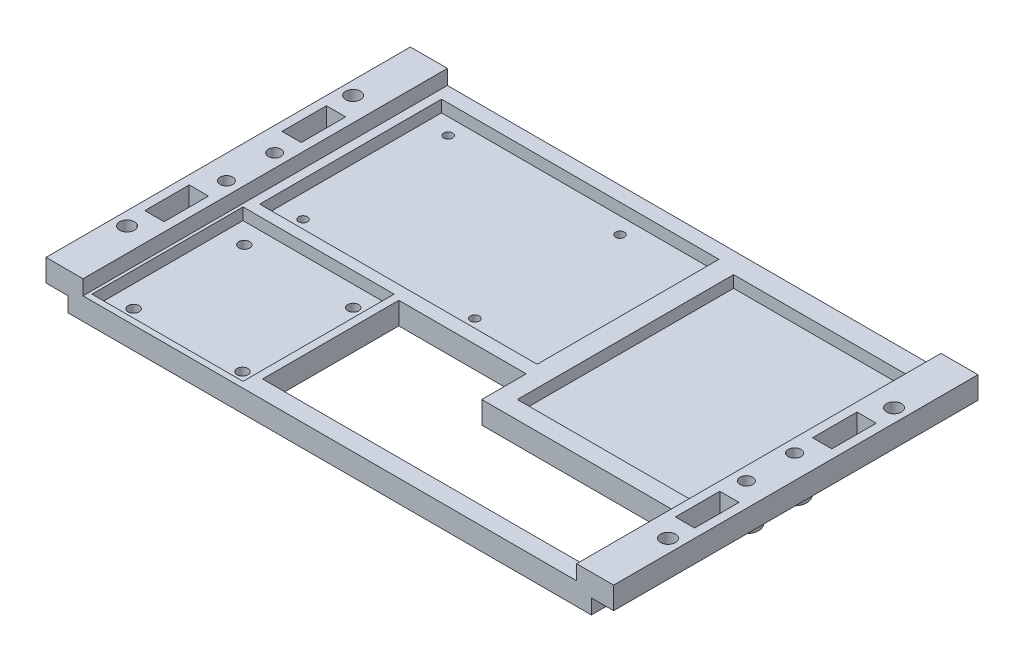
SolidWorks part; units mm, degrees
ref_plane "Front Plane" through (0, 0, 0) normal (0, 0, 1) x (1, 0, 0)
ref_plane "Top Plane" through (0, 0, 0) normal (0, 1, 0) x (1, 0, 0)
ref_plane "Right Plane" through (0, 0, 0) normal (1, 0, 0) x (0, 0, -1)
sketch "Sketch2" plane through (0, 0, 0) normal (0, 0, 1) x (1, 0, 0)
  line L0 (179.1, 12.5) -> (191.6, 12.5)
  line L1 (7.5, 0) -> (184.1, 0)
  line L2 (0, 5) -> (0, 12.5)
  line L3 (0, 12.5) -> (12.5, 12.5)
  line L4 (191.6, 5) -> (191.6, 12.5)
  line L7 (0, 5) -> (7.5, 5)
  line L8 (7.5, 0) -> (7.5, 5)
  line L11 (191.6, 5) -> (184.1, 5)
  line L12 (184.1, 0) -> (184.1, 5)
  line L14 (12.5, 12.5) -> (12.5, 7.5)
  line L15 (12.5, 7.5) -> (179.1, 7.5)
  line L16 (179.1, 12.5) -> (179.1, 7.5)
  dimension "D1" = 191.6
  dimension "D2" = 5
  dimension "D3" = 5
  dimension "D4" = 5
  dimension "D5" = 12.5
  dimension "D6" = 7.5
  dimension "D7" = 7.5
  dimension "D8" = 12.5
  dimension "D9" = 12.5
extrude "PlateFrame" add sketch "Sketch2" along normal blind 150
sketch "Sketch3" plane through (0, 12.5, 0) normal (0, 1, 0) x (1, 0, 0)
  line L0 (12.5, 0) -> (0, 0) construction
  line L2 (0, -150) -> (0, 0) construction
  line L3 (191.6, -150) -> (191.6, 0) construction
  line L4 (191.6, 0) -> (179.1, 0) construction
  circle A0 centre (8.05, -66.85) radius 2.5
  circle A1 centre (8.05, -83.15) radius 2.5
  circle A2 centre (183.55, -66.85) radius 2.5
  circle A3 centre (183.55, -83.15) radius 2.5
  dimension "D1" = 5
  dimension "D2" = 5
  dimension "D3" = 5
  dimension "D4" = 5
  dimension "D5" = 66.85
  dimension "D6" = 16.3
  dimension "D7" = 8.05
  dimension "D8" = 8.05
  dimension "D9" = 8.05
  dimension "D10" = 8.05
  dimension "D11" = 66.85
  dimension "D12" = 16.3
  dimension "D13" = 175.5
extrude "HoleSupport" cut sketch "Sketch3" against normal through all
sketch "Sketch4" plane through (0, 12.5, 0) normal (0, 1, 0) x (1, 0, 0)
  circle A0 centre (8.05, -66.85) radius 2.15
  circle A1 centre (8.05, -83.15) radius 2.15
  circle A2 centre (183.55, -83.15) radius 2.15
  circle A3 centre (183.55, -66.85) radius 2.15
  circle A4 centre (183.55, -66.85) radius 4.15
  circle A5 centre (183.55, -83.15) radius 4.15
  circle A6 centre (8.05, -66.85) radius 4.15
  circle A7 centre (8.05, -83.15) radius 4.15
  dimension "D1" = 2
extrude "CylindricalSupports" add sketch "Sketch4" against normal blind 12.5
sketch "Sketch5" plane through (0, 7.5, 0) normal (0, 1, 0) x (1, 0, 0)
  line L0 (12.5, -150) -> (12.5, 0) construction
  line L1 (17.5, -87) -> (60.5, -87)
  line L2 (12.5, -150) -> (12.5, 0) construction
  line L3 (17.5, -20) -> (107.15, -20)
  line L4 (17.5, -20) -> (17.5, -77.35)
  line L5 (17.5, -77.35) -> (107.15, -77.35)
  line L6 (107.15, -20) -> (107.15, -77.35)
  line L7 (174.1, -20) -> (116.1, -20)
  line L8 (174.1, -20) -> (174.1, -93)
  line L9 (174.1, -93) -> (116.1, -93)
  line L10 (116.1, -20) -> (116.1, -93)
  line L15 (179.1, -150) -> (179.1, 0) construction
  line L16 (179.1, 0) -> (12.5, 0) construction
  line L17 (17.5, -87) -> (17.5, -130)
  line L18 (17.5, -130) -> (60.5, -130)
  line L19 (60.5, -87) -> (60.5, -130)
  line L20 (179.1, -150) -> (12.5, -150) construction
  dimension "D1" = 5
  dimension "D2" = 89.65
  dimension "D3" = 57.35
  dimension "D4" = 5
  dimension "D5" = 43
  dimension "D6" = 58
  dimension "D7" = 43
  dimension "D8" = 20
  dimension "D9" = 20
  dimension "D10" = 5
  dimension "D11" = 73
  dimension "D12" = 20
extrude "ItemLayout" cut sketch "Sketch5" against normal blind 4
sketch "Sketch6" plane through (0, 7.5, 0) normal (0, 1, 0) x (1, 0, 0)
  line L1 (67.1, -84) -> (110.1, -84)
  line L2 (67.1, -84) -> (67.1, -130)
  line L3 (67.1, -130) -> (110.1, -130)
  line L4 (110.1, -84) -> (110.1, -99)
  line L9 (179.1, -150) -> (179.1, 0) construction
  line L10 (110.1, -130) -> (174.1, -130)
  line L12 (110.1, -99) -> (174.1, -99)
  line L13 (174.1, -130) -> (174.1, -99)
  line L14 (116.1, -93) -> (174.1, -93) construction
  line L15 (116.1, -20) -> (116.1, -93) construction
  line L17 (179.1, -150) -> (12.5, -150) construction
  dimension "D1" = 20
  dimension "D2" = 43
  dimension "D3" = 5
  dimension "D4" = 6
  dimension "D5" = 6
  dimension "D6" = 15
extrude "HoleCutout" cut sketch "Sketch6" against normal blind 7.5
sketch "Sketch7" plane through (0, 3.5, 0) normal (0, 1, 0) x (1, 0, 0)
  line L0 (17.5, -20) -> (17.5, -77.35) construction
  line L1 (17.5, -20) -> (17.5, -77.35) construction
  line L2 (107.15, -20) -> (17.5, -20) construction
  line L3 (107.15, -20) -> (17.5, -20) construction
  circle A0 centre (23.26, -23.5) radius 1.5
  circle A1 centre (23.26, -72.5) radius 1.5
  circle A2 centre (81.26, -72.5) radius 1.5
  circle A3 centre (81.26, -23.5) radius 1.5
  dimension "D1" = 3
  dimension "D2" = 3
  dimension "D3" = 3
  dimension "D4" = 3
  dimension "D5" = 5.76
  dimension "D6" = 5.76
  dimension "D7" = 3.5
  dimension "D8" = 3.5
  dimension "D9" = 58
  dimension "D10" = 58
  dimension "D11" = 49
  dimension "D12" = 49
extrude "HoleRaspberryPi" cut sketch "Sketch7" against normal blind 3.5
sketch "Sketch8" plane through (0, 3.5, 0) normal (0, 1, 0) x (1, 0, 0)
  line L0 (17.5, -130) -> (60.5, -130) construction
  line L1 (60.5, -87) -> (17.5, -87) construction
  line L2 (60.5, -130) -> (60.5, -87) construction
  line L3 (60.5, -130) -> (60.5, -87) construction
  line L4 (17.5, -87) -> (17.5, -130) construction
  line L5 (17.5, -130) -> (60.5, -130) construction
  circle A0 centre (57.56, -127.24) radius 1.85
  circle A1 centre (57.56, -89.86) radius 1.85
  circle A2 centre (20.81, -89.86) radius 1.85
  circle A3 centre (20.81, -127.24) radius 1.85
  dimension "D1" = 3.7
  dimension "D2" = 3.7
  dimension "D3" = 3.7
  dimension "D4" = 3.7
  dimension "D6" = 2.86
  dimension "D8" = 2.94
  dimension "D9" = 2.86
  dimension "D10" = 3.31
  dimension "D11" = 2.76
  dimension "D12" = 3.31
  dimension "D5" = 2.76
  dimension "D7" = 2.94
extrude "HoleMotorDriver" cut sketch "Sketch8" against normal blind 3.5
sketch "Sketch10" plane through (0, 7.5, 0) normal (0, 1, 0) x (1, 0, 0)
  line L1 (17.5, -87) -> (60.5, -87)
  line L2 (17.5, -87) -> (17.5, -130)
  line L3 (17.5, -130) -> (60.5, -130)
  line L4 (60.5, -87) -> (60.5, -130)
  line L5 (16.5, -86) -> (61.5, -86)
  line L6 (16.5, -86) -> (16.5, -131)
  line L7 (16.5, -131) -> (61.5, -131)
  line L8 (61.5, -86) -> (61.5, -131)
  dimension "D1" = 1
  dimension "D2" = 1
  dimension "D3" = 1
  dimension "D4" = 1
extrude "CutMotorDriver" cut sketch "Sketch10" against normal blind 4
sketch "Sketch11" plane through (0, 7.5, 0) normal (0, 1, 0) x (1, 0, 0)
  line L1 (17.5, -20) -> (107.15, -20)
  line L2 (17.5, -20) -> (17.5, -77.35)
  line L3 (17.5, -77.35) -> (107.15, -77.35)
  line L4 (107.15, -20) -> (107.15, -77.35)
  line L5 (109.15, -79.35) -> (15.5, -79.35)
  line L6 (109.15, -79.35) -> (109.15, -18)
  line L7 (109.15, -18) -> (15.5, -18)
  line L8 (15.5, -79.35) -> (15.5, -18)
  dimension "D1" = 2
  dimension "D2" = 2
  dimension "D3" = 2
  dimension "D4" = 2
extrude "CutPaspberryPi" cut sketch "Sketch11" against normal blind 4
sketch "Sketch12" plane through (0, 12.5, 0) normal (0, 1, 0) x (1, 0, 0)
  line L0 (191.6, -150) -> (191.6, 0) construction
  line L1 (0, 0) -> (191.6, 0)
  line L2 (0, 0) -> (0, -13)
  line L3 (0, -13) -> (191.6, -13)
  line L4 (191.6, 0) -> (191.6, -13)
  line L6 (0, -150) -> (191.6, -150)
  line L7 (0, -150) -> (0, -136)
  line L8 (0, -136) -> (191.6, -136)
  line L9 (191.6, -150) -> (191.6, -136)
  dimension "D1" = 13
  dimension "D2" = 14
extrude "CutPlateEdges" cut sketch "Sketch12" against normal blind 12.5
sketch "Sketch13" plane through (0, 12.5, 0) normal (0, 1, 0) x (1, 0, 0)
  line L0 (12.5, -136) -> (12.5, -13) construction
  line L1 (9.5, -59.35) -> (3, -59.35)
  line L2 (9.5, -59.35) -> (9.5, -44.35)
  line L3 (9.5, -44.35) -> (3, -44.35)
  line L4 (3, -59.35) -> (3, -44.35)
  line L5 (3, -90.65) -> (9.5, -90.65)
  line L6 (3, -90.65) -> (3, -105.65)
  line L7 (3, -105.65) -> (9.5, -105.65)
  line L8 (9.5, -90.65) -> (9.5, -105.65)
  line L9 (182.1, -59.35) -> (188.6, -59.35)
  line L10 (182.1, -59.35) -> (182.1, -44.35)
  line L11 (182.1, -44.35) -> (188.6, -44.35)
  line L12 (188.6, -59.35) -> (188.6, -44.35)
  line L13 (182.1, -90.65) -> (188.6, -90.65)
  line L14 (182.1, -90.65) -> (182.1, -105.65)
  line L15 (182.1, -105.65) -> (188.6, -105.65)
  line L16 (188.6, -90.65) -> (188.6, -105.65)
  line L18 (179.1, -136) -> (179.1, -13) construction
  line L19 (179.1, -136) -> (179.1, -13) construction
  circle A4 centre (8.05, -66.85) radius 2.15 construction
  circle A5 centre (8.05, -83.15) radius 2.15 construction
  circle A6 centre (183.55, -66.85) radius 2.15 construction
  circle A7 centre (183.55, -83.15) radius 2.15 construction
  dimension "D2" = 7.5
  dimension "D9" = 7.5
  dimension "D10" = 7.5
  dimension "D3" = 3
  dimension "D4" = 6.5
  dimension "D5" = 15
  dimension "D6" = 3
  dimension "D7" = 6.5
  dimension "D8" = 15
  dimension "D11" = 3
  dimension "D12" = 3
  dimension "D13" = 6.5
  dimension "D14" = 6.5
  dimension "D15" = 15
  dimension "D16" = 15
  dimension "D17" = 7.5
extrude "CutShellHoles" cut sketch "Sketch13" against normal blind 12.5
sketch "Sketch14" plane through (0, 7.5, 0) normal (0, 1, 0) x (1, 0, 0)
  line L0 (61.5, -131) -> (61.5, -86) construction
  line L1 (64.5, -83) -> (13.5, -83)
  line L2 (64.5, -83) -> (64.5, -134)
  line L3 (64.5, -134) -> (13.5, -134)
  line L4 (13.5, -83) -> (13.5, -134)
  line L5 (16.5, -86) -> (16.5, -131) construction
  line L6 (16.5, -131) -> (61.5, -131) construction
  line L7 (61.5, -86) -> (16.5, -86) construction
  dimension "D1" = 3
  dimension "D2" = 3
  dimension "D3" = 3
  dimension "D4" = 3
extrude "CutMotorDriver2" cut sketch "Sketch14" against normal blind 4
sketch "Sketch15" plane through (0, 12.5, 0) normal (0, 1, 0) x (1, 0, 0)
  line L0 (12.5, -136) -> (12.5, -13) construction
  line L1 (12.5, -136) -> (12.5, -13) construction
  line L2 (179.1, -136) -> (179.1, -13) construction
  line L3 (179.1, -136) -> (179.1, -13) construction
  circle A0 centre (4.5, -36.85) radius 2.5
  circle A1 centre (4.5, -113.15) radius 2.5
  circle A2 centre (187.1, -113.15) radius 2.5
  circle A3 centre (187.1, -36.85) radius 2.5
  circle A4 centre (8.05, -66.85) radius 2.15 construction
  circle A5 centre (8.05, -83.15) radius 2.15 construction
  circle A6 centre (183.55, -66.85) radius 2.15 construction
  circle A7 centre (183.55, -83.15) radius 2.15 construction
  dimension "D2" = 30
  dimension "D3" = 5
  dimension "D4" = 8
  dimension "D5" = 8
  dimension "D6" = 5
  dimension "D7" = 30
  dimension "D8" = 30
  dimension "D9" = 5
  dimension "D10" = 5
  dimension "D11" = 8
  dimension "D1" = 30
  dimension "D12" = 8
extrude "StandoffHoles" cut sketch "Sketch15" against normal through all
